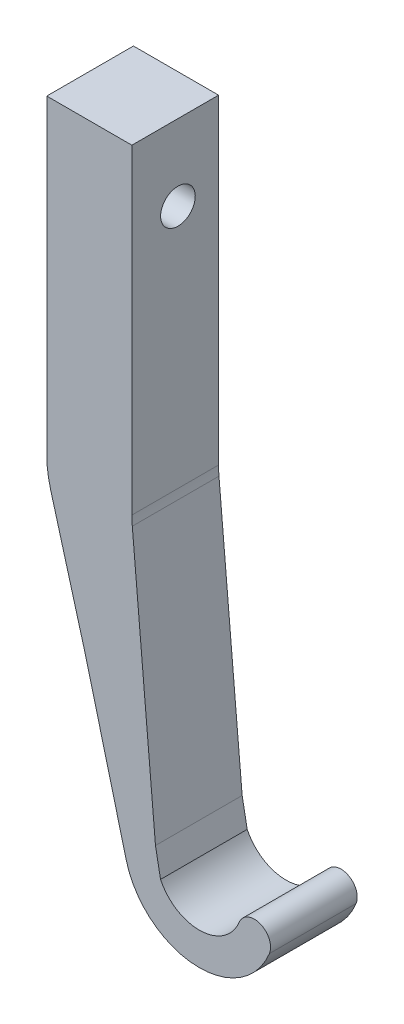
SolidWorks part; units mm, degrees
ref_plane "Alzado" through (0, 0, 0) normal (0, 0, 1) x (1, 0, 0)
ref_plane "Planta" through (0, 0, 0) normal (0, 1, 0) x (1, 0, 0)
ref_plane "Vista lateral" through (0, 0, 0) normal (1, 0, 0) x (0, 0, -1)
sketch "Croquis2" plane through (0, 0, 0) normal (0, 0, 1) x (1, 0, 0)
  line L0 (-3.9536, -0.3459) -> (-6.229, 25.6616)
  line L5 (-6.229, 25.6616) -> (-14.0853, 25.6616) construction
  line L6 (-14.0853, 25.6616) -> (-6.9688, 0)
  line L7 (0, 0) -> (6.8165, 1.4489) construction
  line L8 (13.0373, 0) -> (-14.2625, 0) construction
  line L9 (-14.0853, 25.6616) -> (-14.0853, 55.6616)
  line L10 (-6.229, 25.6616) -> (-6.229, 55.6616)
  line L11 (-6.229, 55.6616) -> (-14.0853, 55.6616)
  line L12 (0, 0) -> (6.4613, -2.6105) construction
  arc A0 (-3.9688, 0) -> (3.882, 0.8251) centre (0, 0) ccw
  arc A1 (-6.9688, 0) -> (6.8165, 1.4489) centre (0, 0) ccw
  arc A2 (3.882, 0.8251) -> (6.8165, 1.4489) centre (5.3492, 1.137) cw
  arc A3 (3.6798, -1.4867) -> (6.4613, -2.6105) centre (5.0705, -2.0486) cw
  point P0 (0, 0)
  point P18 (5.0705, -2.0486)
  dimension "D1" = 7.9375
  dimension "D2" = 3
  dimension "D5" = 1.5
  dimension "D10" = 1.5
  dimension "D3" = 95
  dimension "D4" = 105.5
  dimension "D6" = 12
  dimension "D7" = 30
  dimension "D8" = 25.6616
  dimension "D9" = 7.8563
  dimension "D11" = 22
extrude "Saliente-Extruir2" add sketch "Croquis2" along normal mid plane 8 contours A2 A0 L0 L10 L11 L9 L6 A1 region at (-8.3711, 27.0401, 0)
sketch "Croquis3" plane through (0, 0, 0) normal (0, 0, 1) x (1, 0, 0)
  line L0 (-10.527, 12.8308) -> (-6.7572, -1.7039)
  line L1 (-14.0853, 25.6616) -> (-6.9688, 0) construction
  line L2 (-6.7572, -1.7039) -> (-3.5844, -1.7039)
  line L3 (-3.5844, -1.7039) -> (-6.327, 12.8308)
  line L4 (-6.327, 12.8308) -> (-10.527, 12.8308)
  line L7 (-3.9536, -0.3459) -> (-6.229, 25.6616)
  line L8 (-6.229, 25.6616) -> (-6.229, 55.6616)
  line L9 (-6.229, 55.6616) -> (-14.0853, 55.6616)
  line L10 (-14.0853, 55.6616) -> (-14.0853, 25.6616)
  line L11 (-14.0853, 25.6616) -> (-6.9688, 0)
  line L12 (-3.9536, -0.3459) -> (-6.229, 25.6616)
  line L13 (-6.229, 25.6616) -> (-6.229, 55.6616)
  line L14 (-6.229, 55.6616) -> (-14.0853, 55.6616)
  line L15 (-14.0853, 55.6616) -> (-14.0853, 25.6616)
  line L16 (-14.0853, 25.6616) -> (-6.9688, 0)
  arc A0 (-6.9688, 0) -> (6.4613, -2.6105) centre (0, 0) ccw construction
  arc A4 (6.4613, -2.6105) -> (3.6798, -1.4867) centre (5.0705, -2.0486) ccw
  arc A5 (-3.9536, -0.3459) -> (3.6798, -1.4867) centre (0, 0) ccw
  arc A6 (-6.9688, 0) -> (6.4613, -2.6105) centre (0, 0) ccw
  arc A8 (-3.9536, -0.3459) -> (3.6798, -1.4867) centre (0, 0) ccw
  arc A9 (-6.9688, 0) -> (6.4613, -2.6105) centre (0, 0) ccw
  arc A10 (6.4613, -2.6105) -> (3.6798, -1.4867) centre (5.0705, -2.0486) ccw
  dimension "D2" = 4.2
  dimension "D3" = 3.1729
  dimension "D1" = 0
extrude "Saliente-Extruir3" add sketch "Croquis3" along normal mid plane 8 contours L4 L0 L2 L3
fillet "Redondeo1" radius 10 1 edges at (-14.0853, 25.6616, 0)
fillet "Redondeo2" radius 10 1 edges at (-6.229, 25.6616, 0)
sketch "Croquis4" plane through (-14.0853, 0, 0) normal (-1, 0, 0) x (0, 0, 1)
  circle A0 centre (-0.25, 48.6616) radius 1.6
  dimension "D1" = 3.2
extrude "Cortar-Extruir1" cut sketch "Croquis4" against normal blind 21.5
